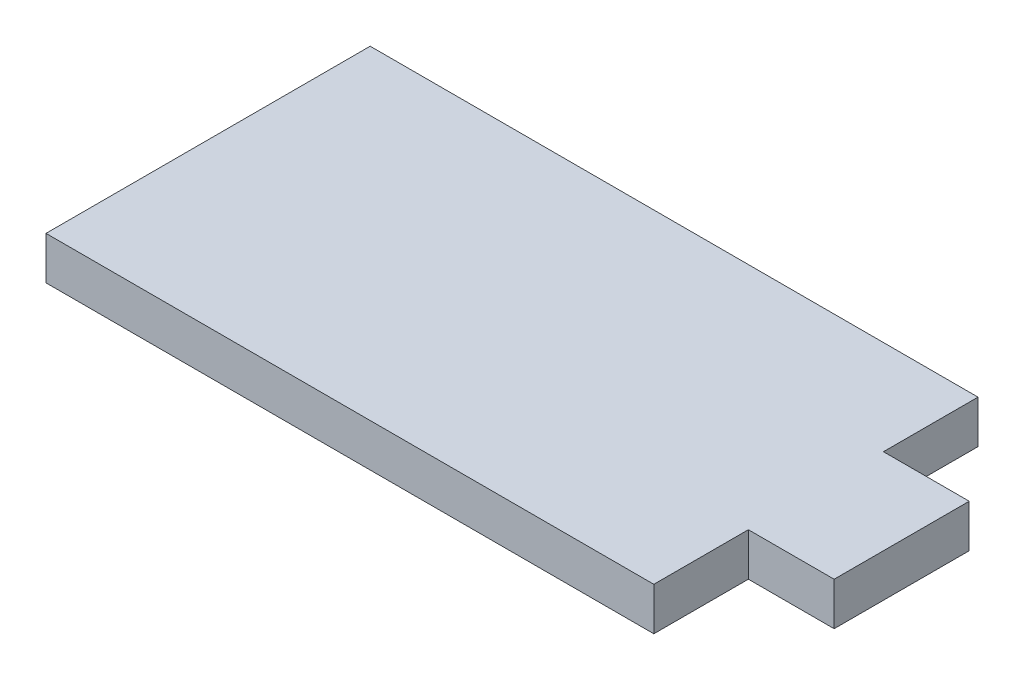
SolidWorks part; units mm, degrees
ref_plane "Front Plane" through (0, 0, 0) normal (0, 0, 1) x (1, 0, 0)
ref_plane "Top Plane" through (0, 0, 0) normal (0, 1, 0) x (1, 0, 0)
ref_plane "Right Plane" through (0, 0, 0) normal (1, 0, 0) x (0, 0, -1)
sketch "Sketch1" plane through (0, 0, 0) normal (0, 1, 0) x (1, 0, 0)
  line L0 (-22.5, 7) -> (22.5, 7)
  line L1 (22.5, 7) -> (22.5, 0)
  line L2 (22.5, 0) -> (28.85, 0)
  line L3 (28.85, 0) -> (28.85, -10)
  line L4 (28.85, -10) -> (22.5, -10)
  line L5 (22.5, -10) -> (22.5, -17)
  line L6 (22.5, -17) -> (-22.5, -17)
  line L7 (-22.5, -17) -> (-22.5, -10)
  line L8 (-22.5, -10) -> (-28.85, -10)
  line L9 (-28.85, -10) -> (-28.85, 0)
  line L10 (-28.85, 0) -> (-22.5, 0)
  line L11 (-22.5, 0) -> (-22.5, 7)
  line L12 (-22.5, 0) -> (-22.5, -10) construction
  point P11 (0, 7)
  point P14 (-28.85, -5)
  dimension "D1" = 6.35
  dimension "D2" = 10
  dimension "D3" = 45
  dimension "D4" = 24
extrude "Boss-Extrude1" add sketch "Sketch1" along normal blind 3.175 contours L11 L12 L7 L6 L5 L4 L3 L2 L1 L0 region at (1.4258, 0, 5)
equation "\"length\"= 24mm"
equation "\"w_mach\"= 45mm"
equation "\"w_tab\"= 10mm"
equation "\"t_wood\"= 0.125in"
equation "\"t_side\"= 0.25in"
equation "\"D1@Sketch1\"=\"t_side\""
equation "\"D2@Sketch1\"=\"w_tab\""
equation "\"D3@Sketch1\"=\"w_mach\""
equation "\"D4@Sketch1\"=\"length\""
equation "\"D1@Boss-Extrude1\"=\"t_wood\""
